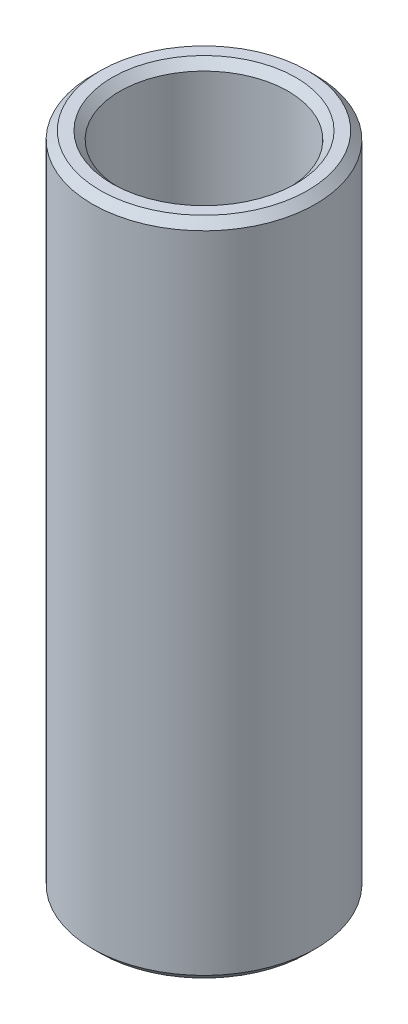
SolidWorks part; units mm, degrees
ref_plane "Front Plane" through (0, 0, 0) normal (0, 0, 1) x (1, 0, 0)
ref_plane "Top Plane" through (0, 0, 0) normal (0, 1, 0) x (1, 0, 0)
ref_plane "Right Plane" through (0, 0, 0) normal (1, 0, 0) x (0, 0, -1)
sketch "Sketch1" plane through (0, 0, 0) normal (0, 1, 0) x (1, 0, 0)
  circle A0 centre (0, 0) radius 15
  dimension "SLEEVE_OD" = 30
extrude "Boss-Extrude1" add sketch "Sketch1" along normal blind 88.7655
sketch "Sketch2" plane through (0, 0, 0) normal (0, 1, 0) x (1, 0, 0)
  circle A0 centre (0, 0) radius 11.2977
  dimension "BORE_D" = 22.5955
extrude "Cut-Extrude1" cut sketch "Sketch2" along normal through all
chamfer "Chamfer1" distance 1.0606 angle 45 4 edges at (0, 88.7655, 11.2977) (0, 0, 11.2977) (0, 0, 15) (0, 88.7655, 15)
